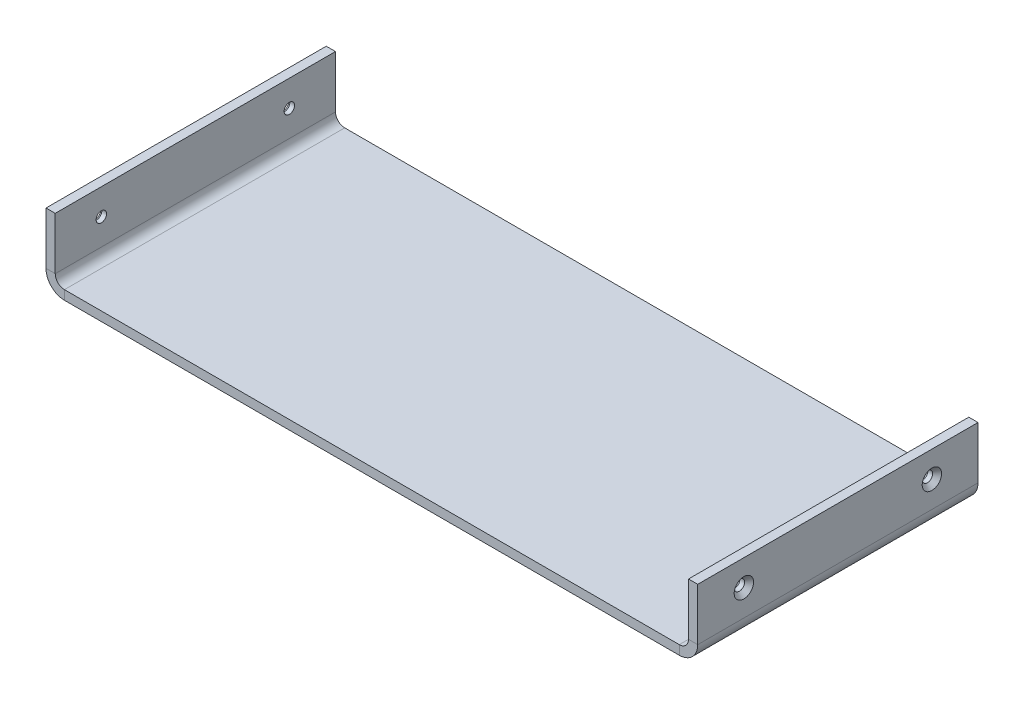
SolidWorks part; units mm, degrees
note: The reader was unsure of these and kept them because the rebuilt part matched: thickness of "Базовая кромка1", "Ребро-кромка1", "Листовой металл3", "Листовой металл4", "Листовой металл5"; flange length of "Ребро-кромка1".
ref_plane "Спереди" through (0, 0, 0) normal (0, 0, 1) x (1, 0, 0)
ref_plane "Сверху" through (0, 0, 0) normal (0, 1, 0) x (1, 0, 0)
ref_plane "Справа" through (0, 0, 0) normal (1, 0, 0) x (0, 0, -1)
sketch "Эскиз1" plane through (0, 0, 0) normal (0, 1, 0) x (1, 0, 0)
  line L1 (100, -45.58) -> (-100, -45.58)
  line L2 (100, -45.58) -> (100, 45.58)
  line L3 (100, 45.58) -> (-100, 45.58)
  line L4 (-100, -45.58) -> (-100, 45.58)
  line L5 (100, -45.58) -> (-100, 45.58) construction
  line L6 (100, 45.58) -> (-100, -45.58) construction
  point P0 (0, 0)
  dimension "D1" = 200
  dimension "D2" = 91.16
base flange "Базовая кромка1" sketch "Эскиз1" thickness 3 reverse thickness direction no parameters "D1"=1.6
edge flange "Ребро-кромка1" sketch "Эскиз10" flange profiles "Эскиз10", "Эскиз11" flange angle 90 flange length 23 flange position bend outside bend radius 3 thickness 3 relief rectangular parameters "D6"=10, "D8"=1
sketch "Эскиз10" plane through (-100, 0, 0) normal (-1, 0, 0) x (0, 0, 1)
  line L2 (-45.58, 0) -> (-45.58, 20)
  line L3 (-45.58, 20) -> (45.58, 20)
  line L4 (45.58, 20) -> (45.58, 0)
  line L11 (-45.58, 0) -> (45.58, 0) construction
  line L12 (-45.58, 0) -> (45.58, 0)
  dimension "D2" = 20
sketch "Эскиз11" plane through (100, 0, 0) normal (1, 0, 0) x (0, 0, -1)
  line L0 (-45.58, 0) -> (45.58, 0) construction
  line L1 (-45.58, 0) -> (45.58, 0)
  line L2 (-45.58, 0) -> (-45.58, 20)
  line L3 (-45.58, 20) -> (45.58, 20)
  line L4 (45.58, 20) -> (45.58, 0)
bend "EdgeBend1" bend radius 3 bend angle 90 parameters "D5"=1
bend "EdgeBend2" bend radius 3 bend angle 90 parameters "D5"=2
hole_wizard "Зенковка для  винта с плоской головкой M31" positions "Трехмерный эскиз1" profile "Эскиз12" countersink size "M3" standard "Ansi Metric"
sketch3d "Трехмерный эскиз1"
  line L0 (106, 11.5, 45.58) -> (106, 11.5, -45.58) construction
  line L1 (106, 20, 45.58) -> (106, 3, 45.58) construction
  line L2 (106, 3, -45.58) -> (106, 20, -45.58) construction
  point P0 (106, 11.5223, 30.58)
  point P2 (106, 11.5, -30.58)
  point P15 (-106, 11.5, -30.58)
  point P17 (-106, 11.5223, 30.58)
  dimension "D1" = 15
  dimension "D2" = 15
sketch "Эскиз12" plane through (106, 11.5223, 30.58) normal (0, 1, 0) x (0, 0, -1)
  line L0 (0, 0) -> (0, 9.5215)
  line L1 (0, 9.5215) -> (1.7, 8.5)
  line L2 (1.7, 8.5) -> (1.7, 1.45)
  line L3 (1.7, 1.45) -> (3.15, 0)
  line L5 (3.15, 0) -> (0, 0)
  line L6 (-1.7, 1.45) -> (-3.15, 0) construction
  line L10 (0, 9.5215) -> (-1.7, 8.5) construction
  line L11 (0, -6.35) -> (0, 107.95) construction
  dimension "Диаметр отверстия" = 3.4
  dimension "Глубина отверстия" = 8.5
  dimension "Диаметр передней зенковки" = 6.3
  dimension "Угол передней зенковки" = 90
  dimension "Угол заточки сверла" = 118
sketch "Сгиб-Линии1" plane through (0, 0, 0) normal (0, 1, 0) x (1, 0, 0)
sketch "Граничная рамка1" plane through (0, 0, 0) normal (0, 1, 0) x (1, 0, 0)
sheet metal parameters "Листовой металл3" thickness 3 parameters "D1"=1.6
flat pattern "Развертка3" [suppressed]
sketch "Сгиб-Линии2" plane through (0, 0, 0) normal (0, 1, 0) x (1, 0, 0)
sketch "Граничная рамка2" [suppressed] plane through (0, 0, 0) normal (0, 1, 0) x (1, 0, 0)
sheet metal parameters "Листовой металл4" thickness 3 parameters "D1"=1.6, "D7"=2
flat pattern "Развертка3" [suppressed]
sketch "Сгиб-Линии2" plane through (0, 0, 0) normal (0, 1, 0) x (1, 0, 0)
sketch "Граничная рамка2" [suppressed] plane through (0, 0, 0) normal (0, 1, 0) x (1, 0, 0)
bend of the flat pattern "Плоское состояние-<EdgeBend1>1"
bend of the flat pattern "Плоское состояние-<EdgeBend2>1"
sheet metal parameters "Листовой металл5" thickness 3 parameters "D1"=1.6, "D7"=2
flat pattern "Развертка3" [suppressed]
sketch "Сгиб-Линии2" plane through (0, 0, 0) normal (0, 1, 0) x (1, 0, 0)
sketch "Граничная рамка2" [suppressed] plane through (0, 0, 0) normal (0, 1, 0) x (1, 0, 0)
bend of the flat pattern "Плоское состояние-<EdgeBend1>1"
bend of the flat pattern "Плоское состояние-<EdgeBend2>1"
